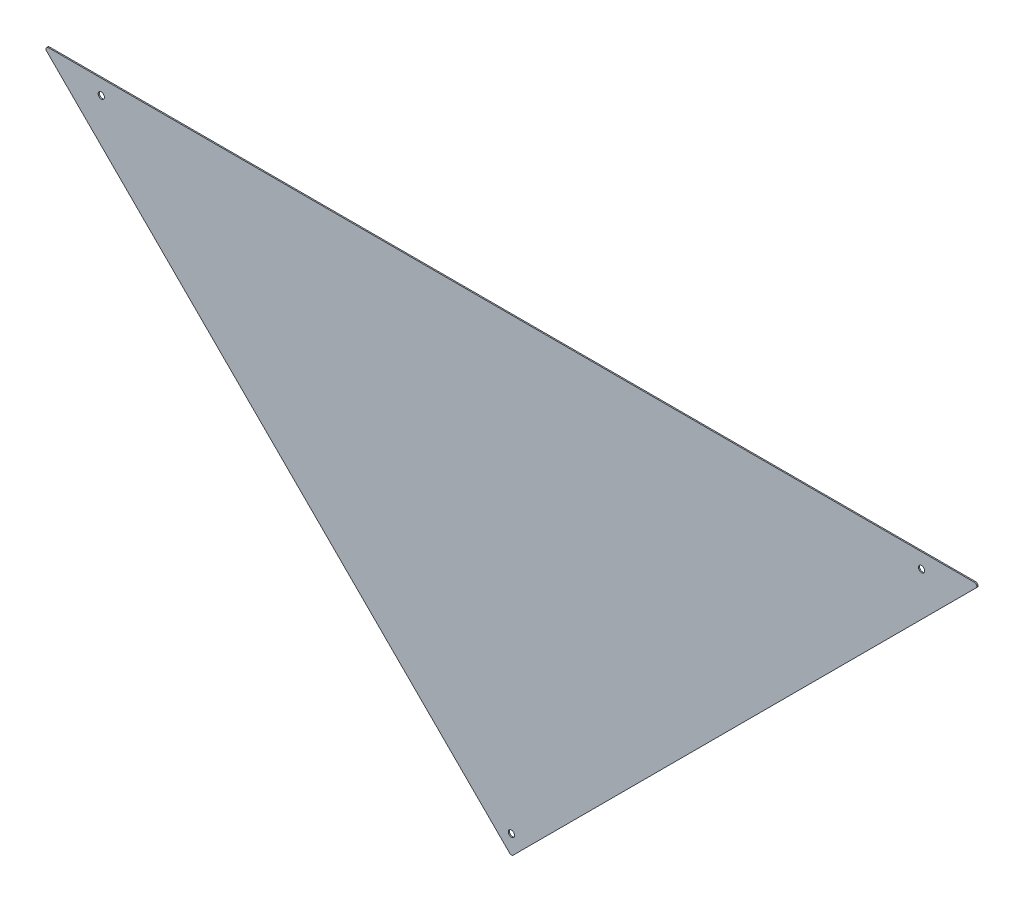
SolidWorks part; units mm, degrees
material "Plain Carbon Steel"
ref_plane "Front Plane" through (0, 0, 0) normal (0, 0, 1) x (1, 0, 0)
ref_plane "Top Plane" through (0, 0, 0) normal (0, 1, 0) x (1, 0, 0)
ref_plane "Right Plane" through (0, 0, 0) normal (1, 0, 0) x (0, 0, -1)
sketch "Sketch1" plane through (0, 0, 0) normal (0, 0, 1) x (1, 0, 0)
  line L2 (2.1213, 6.364) -> (594.8787, 599.1213)
  line L3 (592.7574, 604.2426) -> (-592.7574, 604.2426)
  line L4 (-594.8787, 599.1213) -> (-2.1213, 6.364)
  line L5 (600.7574, 605) -> (525, 529.2426) construction
  line L6 (-525, 529.2426) -> (-600.7574, 605) construction
  circle A0 centre (0, 29.2426) radius 2.4 construction
  circle A1 centre (-525, 585) radius 2.4 construction
  arc A2 (594.8787, 599.1213) -> (592.7574, 604.2426) centre (592.7574, 601.2426) ccw
  arc A3 (-592.7574, 604.2426) -> (-594.8787, 599.1213) centre (-592.7574, 601.2426) ccw
  arc A4 (2.1213, 6.364) -> (-2.1213, 6.364) centre (0, 8.4853) cw
  circle A17 centre (-525, 585) radius 4
  circle A18 centre (525, 585) radius 4
  circle A19 centre (0, 29.2426) radius 4
  circle A20 centre (525, 585) radius 2.4 construction
  point P23 (600, 604.2426)
  point P26 (-600, 604.2426)
  point P29 (0, 4.2426)
  dimension "D2" = 3
  dimension "D3" = 3
  dimension "D4" = 8
  dimension "D1" = 1200
extrude "Boss-Extrude1" add sketch "Sketch1" along normal blind 1.5 contours A4 L2 A2 L3 A3 L4 region at (0, 404.2344, 0)
sketch "Sketch2" plane through (0, 0, 1.5) normal (0, 0, 1) x (1, 0, 0)
  line L0 (-600, 604.2426) -> (0, 4.2426) construction
  line L1 (0, 4.2426) -> (600, 604.2426) construction
  line L2 (600, 604.2426) -> (-600, 604.2426) construction
  line L3 (592.7574, 604.2426) -> (-592.7574, 604.2426) construction
  line L4 (-594.8787, 599.1213) -> (-2.1213, 6.364) construction
  line L5 (2.1213, 6.364) -> (594.8787, 599.1213) construction
